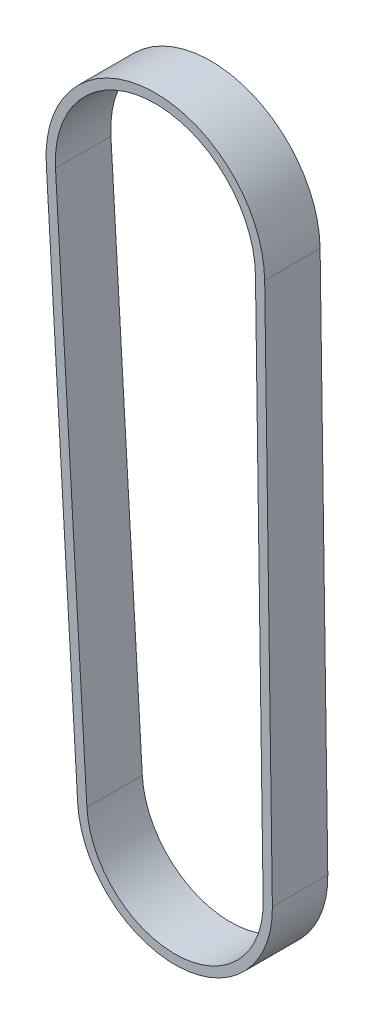
SolidWorks part; units mm, degrees
ref_plane "Front Plane" through (0, 0, 0) normal (0, 0, 1) x (1, 0, 0)
ref_plane "Top Plane" through (0, 0, 0) normal (0, 1, 0) x (1, 0, 0)
ref_plane "Right Plane" through (0, 0, 0) normal (1, 0, 0) x (0, 0, -1)
sketch "Sketch2" plane through (0, 0, 0) normal (0, 0, 1) x (1, 0, 0)
  line L0 (0, 0) -> (1, 0) construction
  line L1 (0, 0) -> (0, 1) construction
  line L6 (-11.1246, -88.2771) -> (-16.2224, -0.947)
  line L7 (16.2483, 0.232) -> (17.4975, -87.2378)
  arc A2 (17.4975, -87.2378) -> (-11.1246, -88.2771) centre (3.175, -87.4424) cw
  arc A3 (-16.2224, -0.947) -> (16.2483, 0.232) centre (0, 0) cw
extrude "Extrude-Thin1" add sketch "Sketch2" against normal blind 9 thin thin type one direction wall 1.5
